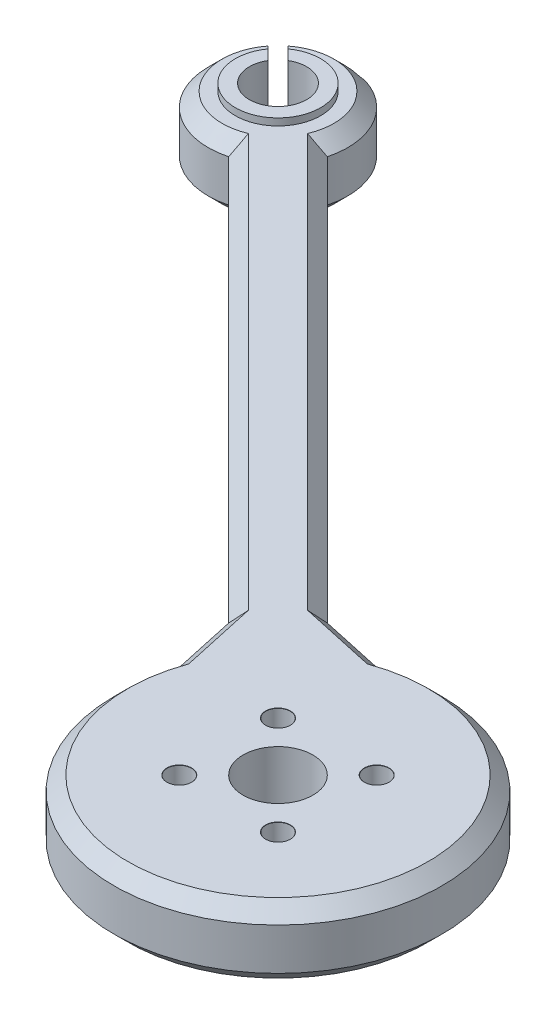
SolidWorks part; units mm, degrees
note: The reader was unsure of these and kept them because the rebuilt part matched: shared geometry of "Sketch1<8>", "Sketch1<11>".
ref_plane "Front Plane" through (0, 0, 0) normal (0, 0, 1) x (1, 0, 0)
ref_plane "Top Plane" through (0, 0, 0) normal (0, 1, 0) x (1, 0, 0)
ref_plane "Right Plane" through (0, 0, 0) normal (1, 0, 0) x (0, 0, -1)
sketch "Sketch1" plane through (0, 0, 0) normal (0, 1, 0) x (1, 0, 0)
  line L0 (7.7499, 7.7499) -> (-7.7501, -7.7501)
  line L1 (-7.7501, 7.7499) -> (7.7499, 7.7499)
  line L2 (-7.7501, 7.7499) -> (-7.7501, -7.7501)
  line L3 (-7.7501, -7.7501) -> (7.7499, -7.7501)
  line L4 (7.7499, 7.7499) -> (7.7499, -7.7501)
  line L5 (-3.21, -7.7501) -> (7.7501, 3.21)
  line L6 (-3.21, -7.7501) -> (-7.7501, -3.21)
  line L7 (7.7501, 3.21) -> (3.21, 7.7501)
  line L8 (-7.7501, -3.21) -> (3.21, 7.7501)
  line L9 (-3.21, -7.7501) -> (3.21, 7.7501) construction
  line L10 (7.7501, 3.21) -> (-7.7501, -3.21) construction
  line L11 (-20.1525, -20.1525) -> (20.1525, 20.1525)
  line L12 (20.5649, -11.3725) -> (24.2176, -15.0252)
  line L13 (-16.617, -16.617) -> (-5.2153, -28.0188)
  line L14 (-19.7721, 12.701) -> (-82.2646, 75.1936)
  line L15 (6.7352, -6.7352) -> (-6.7352, 6.7352) construction
  line L16 (-10.253, 10.253) -> (10.253, -10.253) construction
  line L17 (-12.701, 19.7721) -> (-75.1936, 82.2646)
  line L18 (-88.3715, 86.9573) -> (-92.5955, 91.1813)
  line L19 (-86.9573, 88.3715) -> (-91.1813, 92.5955)
  circle A8 centre (0, 0) radius 23.5
  circle A9 centre (0, 0) radius 5
  circle A12 centre (0, 0) radius 28.5
  circle A13 centre (-84.8528, 84.8528) radius 10
  circle A14 centre (-84.8528, 84.8528) radius 4.1
  circle A15 centre (-84.8528, 84.8528) radius 4.1
  circle A16 centre (-84.8528, 84.8528) radius 2
  point P7 (0, 0)
  dimension "D1" = 15.5
  dimension "D3" = 47
  dimension "D4" = 57
  dimension "D8" = 10
  dimension "D15" = 10
  dimension "D19" = 120
  dimension "D22" = 1
  dimension "D17" = 20
  dimension "D18" = 8.2
  dimension "D20" = 4
  dimension "D2" = 15.5
  dimension "D5" = 15.5
  dimension "D6" = 0
  dimension "D7" = 0
  dimension "D10" = 19.05
  dimension "D11" = 9.525
  dimension "D12" = 30
  dimension "D13" = 10.96
  dimension "D14" = 10.9603
  dimension "D16" = 5
  dimension "D21" = 1
extrude "Boss-Extrude1" add sketch "Sketch1" along normal blind 10
extrude "Boss-Extrude2" add sketch "Sketch1<8>" along normal blind 10
sketch "Sketch1<8>" plane through (0, 0, 0) normal (0, 1, 0) x (1, 0, 0) same geometry as "Sketch1"
extrude "Boss-Extrude3" add sketch "Sketch1<11>" along normal blind 10 contours A13 A14
sketch "Sketch1<11>" plane through (0, 0, 0) normal (0, 1, 0) x (1, 0, 0) same geometry as "Sketch1"
sketch "Sketch3" plane through (0, 10, 0) normal (0, 1, 0) x (1, 0, 0)
  circle A0 centre (-84.8528, 84.8528) radius 6.1
  circle A1 centre (-84.8528, 84.8528) radius 4.1
  arc M5 (-86.9573, 88.3715) -> (-88.3715, 86.9573) centre (-84.8528, 84.8528) cw
  line M12 (-91.1813, 92.5955) -> (-86.9573, 88.3715)
  line M13 (-88.3715, 86.9573) -> (-92.5955, 91.1813)
  dimension "D1" = 2
extrude "Boss-Extrude4" add sketch "Sketch3" along normal blind 1 contours A0 M13 M12 M5
sketch "Sketch4" plane through (-0.7071, 0, 0.7071) normal (0.7071, 0, -0.7071) x (-0.7071, 0, -0.7071)
  line L0 (111.3397, 0) -> (129.9499, 0) construction
  line L1 (129.9499, 10) -> (129.9499, 0) construction
  circle A0 centre (126.9499, 5) radius 1.5
  dimension "D1" = 3
  dimension "D2" = 5
  dimension "D3" = 3
extrude "Cut-Extrude3" cut sketch "Sketch4" along normal through all both and the other way through all
ref_plane "Plane1" through (-7.0711, 0, 7.0711) normal (-0.7071, 0, 0.7071) x (0.7071, 0, 0.7071)
sketch "Sketch6" plane through (-7.0711, 0, 7.0711) normal (-0.7071, 0, 0.7071) x (0.7071, 0, 0.7071)
  circle A0 centre (-126.9499, 5) radius 3
  dimension "D1" = 6
extrude "Cut-Extrude4" cut sketch "Sketch6" against normal offset from surface (6 mm away) 3 up to face at (-89.4136, 5, -87.9994)
chamfer "Chamfer2" distance 5 angle 45 2 edges at (-19.7721, 5, -12.701) (-12.701, 5, -19.7721)
sketch "Sketch7" plane through (0, 10, 0) normal (0, 1, 0) x (1, 0, 0)
  line L0 (7.0711, -7.0711) -> (0, 0) construction
  line L1 (0, 0) -> (0, -10) construction
  line L2 (-7.0711, -7.0711) -> (0, 0) construction
  line L3 (-7.0711, 7.0711) -> (0, 0) construction
  line L4 (7.0711, 7.0711) -> (0, 0) construction
  circle A0 centre (0, 0) radius 10 construction
  point P0 (0, 0)
  point P6 (7.0711, -7.0711)
  point P12 (0, 0)
  point P15 (7.0711, 7.0711)
  point P18 (-7.0711, 7.0711)
  point P21 (-7.0711, -7.0711)
  dimension "D1" = 20
  dimension "D2" = 45
  dimension "D3" = 4
hole_wizard "Ø3.0mm Dowel Hole1" positions "Sketch7" profile "Sketch8" hole size "Ø3.0" standard "ISO"
sketch "Sketch8" plane through (-7.0711, 10, 7.0711) normal (1, 0, 0) x (0, 0, 1)
  line L0 (0, 0) -> (0, 21.0515)
  line L1 (0, 21.0515) -> (1.75, 20)
  line L2 (1.75, 20) -> (1.75, 0.025)
  line L3 (1.75, 0.025) -> (1.775, 0)
  line L5 (1.775, 0) -> (0, 0)
  line L6 (-1.75, 0.025) -> (-1.775, 0) construction
  line L10 (0, 21.0515) -> (-1.75, 20) construction
  line L11 (0, -6.35) -> (0, 107.95) construction
  dimension "Hole Dia." = 3.5
  dimension "Hole Depth" = 20
  dimension "Near C'Sink Dia." = 3.55
  dimension "Near C'Sink Angle" = 90
  dimension "Drill Angle" = 118
chamfer "Chamfer3" distance 2 angle 45 17 edges at (-12.4251, 10, -23.3304) (-12.4251, 0, -23.3304) (-46.2601, 0, -53.3312) (-79.4255, 10, -93.2519) (-79.4255, 0, -93.2519) (-89.0693, 0, -90.4835) (-81.9537, 0, -81.9537) (-90.4835, 0, -89.0693) (-93.2519, 10, -79.4255) (-93.2519, 0, -79.4255) (-53.3312, 0, -46.2601) (-23.3304, 10, -12.4251) (-23.3304, 0, -12.4251) (16.617, 10, 16.617) (16.617, 0, 16.617) (-46.2601, 10, -53.3312) (-53.3312, 10, -46.2601)
ref_plane "Plane2" through (7.7782, 0, -7.7782) normal (-0.7071, 0, 0.7071) x (0.7071, 0, 0.7071)
sketch "Sketch9" plane through (7.7782, 0, -7.7782) normal (-0.7071, 0, 0.7071) x (0.7071, 0, 0.7071)
  line L1 (-124.9291, 8.5) -> (-128.9706, 8.5)
  line L2 (-128.9706, 8.5) -> (-130.9913, 5)
  line L3 (-130.9913, 5) -> (-128.9706, 1.5)
  line L4 (-128.9706, 1.5) -> (-124.9291, 1.5)
  line L5 (-124.9291, 1.5) -> (-122.9084, 5)
  line L6 (-122.9084, 5) -> (-124.9291, 8.5)
  circle A0 centre (-126.9499, 5) radius 3.5 construction
  dimension "D1" = 7
extrude "Cut-Extrude6" cut sketch "Sketch9" along normal blind 6
